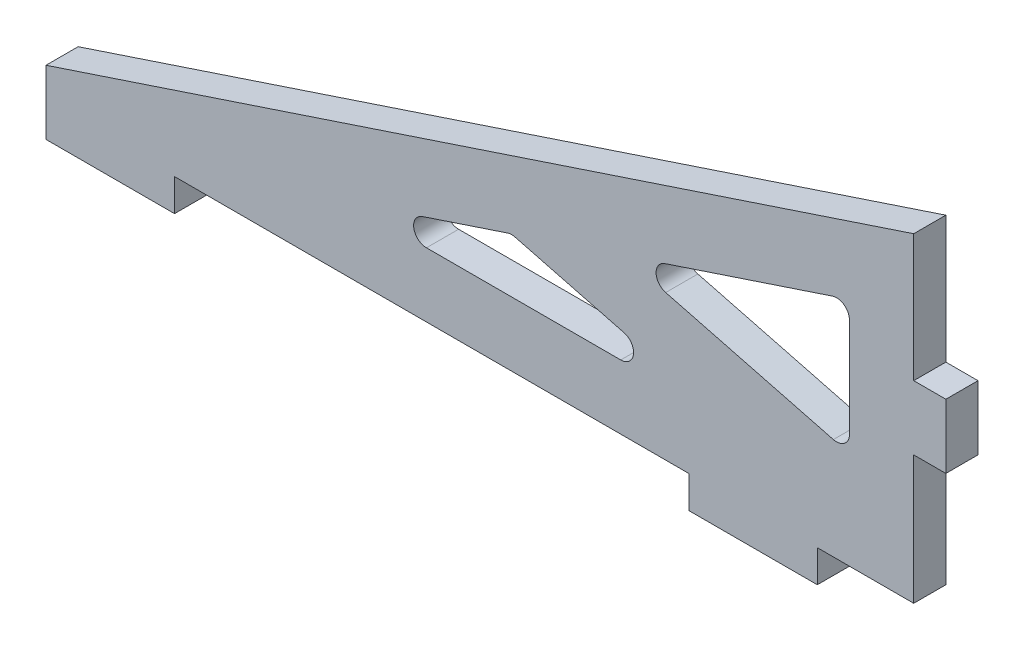
SolidWorks part; units mm, degrees
ref_plane "Front Plane" through (0, 0, 0) normal (0, 0, 1) x (1, 0, 0)
ref_plane "Top Plane" through (0, 0, 0) normal (0, 1, 0) x (1, 0, 0)
ref_plane "Right Plane" through (0, 0, 0) normal (1, 0, 0) x (0, 0, -1)
sketch "Sketch2" plane through (0, 0, 0) normal (0, 0, 1) x (1, 0, 0)
  line L0 (-92.95, 148.308) -> (78.5, 205.204)
  line L1 (78.5, 205.204) -> (84.85, 205.204) construction
  line L2 (84.85, 205.204) -> (84.85, 180.058) construction
  line L4 (-118.35, 135.608) -> (-118.35, 141.958) construction
  line L5 (84.85, 167.358) -> (84.85, 141.958) construction
  line L6 (84.85, 180.058) -> (78.5, 180.058)
  line L8 (84.85, 167.358) -> (78.5, 167.358)
  line L9 (78.5, 180.058) -> (78.5, 167.358) construction
  line L10 (-92.95, 135.608) -> (-92.95, 148.308) construction
  line L13 (-67.55, 141.958) -> (-67.55, 135.608)
  line L15 (34.05, 135.608) -> (34.05, 141.958)
  line L17 (59.45, 141.958) -> (59.45, 135.608)
  line L19 (-92.95, 135.608) -> (-118.35, 135.608) construction
  line L20 (-92.95, 141.958) -> (-92.95, 135.608)
  line L21 (-92.95, 141.958) -> (-92.95, 148.308)
  line L22 (-92.95, 135.608) -> (-67.55, 135.608)
  line L23 (-67.55, 141.958) -> (34.05, 141.958)
  line L24 (34.05, 135.608) -> (59.45, 135.608)
  line L25 (59.45, 141.958) -> (78.5, 141.958)
  line L26 (78.5, 167.358) -> (78.5, 141.958)
  line L27 (84.85, 167.358) -> (84.85, 180.058)
  line L28 (78.5, 180.058) -> (78.5, 205.204)
  point P3 (0, 0)
  point P6 (0, 0)
  dimension "D1" = 6.35
  dimension "D2" = 6.35
  dimension "D3" = 6.35
  dimension "D4" = 12.7
  dimension "D5" = 6.35
  dimension "D6" = 25.4
  dimension "D7" = 25.4
  dimension "D8" = 25.4
  dimension "D9" = 25.4
  dimension "D10" = 6.35
  dimension "D11" = 25.4
extrude "Boss-Extrude1" add sketch "Sketch2" along normal blind 6.35
sketch "Sketch3" plane through (0, 0, 6.35) normal (0, 0, 1) x (1, 0, 0)
  line L0 (-33.4926, 154.658) -> (65.8, 187.6084)
  line L1 (65.8, 187.6084) -> (65.8, 154.658)
  line L2 (65.8, 154.658) -> (-33.4926, 154.658)
  line L3 (78.5, 205.204) -> (-92.95, 148.308) construction
  line L4 (-67.55, 141.958) -> (34.05, 141.958) construction
  line L6 (65.8, 154.658) -> (-19.3713, 176.756) construction
  line L7 (64.2053, 148.5115) -> (-20.9661, 170.6095)
  line L8 (67.3947, 160.8045) -> (-17.7766, 182.9025)
  line L9 (78.5, 180.058) -> (78.5, 205.204) construction
  arc A0 (64.2053, 148.5115) -> (67.3947, 160.8045) centre (65.8, 154.658) ccw
  arc A1 (-17.7766, 182.9025) -> (-20.9661, 170.6095) centre (-19.3713, 176.756) ccw
  point P10 (23.2143, 165.707)
  dimension "D4" = 6.35
  dimension "D1" = 12.7
  dimension "D2" = 12.7
  dimension "D3" = 12.7
extrude "Cut-Extrude1" cut sketch "Sketch3" against normal through all contours L2 L7 L0 | L8 L1 L0 region at (2.001, 158.2501, 6.35) region at (50.9232, 173.8748, 6.35)
fillet "Fillet1" radius 2.54 6 edges at (65.8, 187.6084, 3.175) (21.1696, 172.7978, 3.175) (-1.0194, 165.4343, 3.175) (40.5151, 154.658, 3.175) (-33.4926, 154.658, 3.175) (65.8, 161.2182, 3.175)
